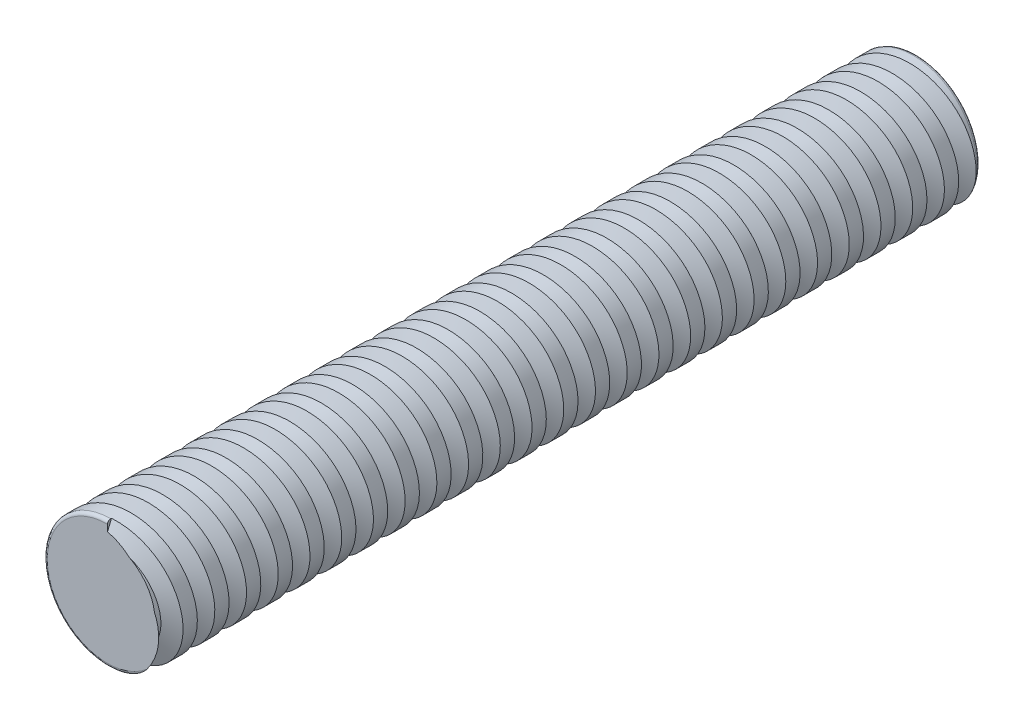
SolidWorks part; units mm, degrees
material "1.5714 (16NiCr4)"
ref_plane "Front Plane" through (0, 0, 0) normal (0, 0, 1) x (1, 0, 0)
ref_plane "Top Plane" through (0, 0, 0) normal (0, 1, 0) x (1, 0, 0)
ref_plane "Right Plane" through (0, 0, 0) normal (1, 0, 0) x (0, 0, -1)
sketch "Sketch1" plane through (0, 0, 0) normal (0, 0, 1) x (1, 0, 0)
  circle A0 centre (0, 0) radius 4
  dimension "D1" = 8
extrude "Boss-Extrude1" add sketch "Sketch1" against normal blind 51
fillet "Fillet1" radius 0.2 2 edges at (4, 0, -51) (4, 0, 0)
sketch "Sketch2" plane through (0, 0, 0) normal (0, 0, 1) x (1, 0, 0)
  circle A0 centre (0, 0) radius 4
  dimension "D1" = 8
sketch "Sketch3" plane through (0, 0, 0) normal (0, 1, 0) x (1, 0, 0)
  line L0 (3, 0.35) -> (3, 0.05)
  line L1 (3, 0.05) -> (5, -0.75)
  line L2 (5, -0.75) -> (5, 1.15)
  line L3 (5, 1.15) -> (3, 0.35)
  line L4 (5, 0.2) -> (3, 0.2)
  line L7 (4, 0.2) -> (-4, 0.2) construction
  point P7 (4, 0.2)
  dimension "D1" = 1.9
  dimension "D2" = 2
  dimension "D3" = 0.3
  dimension "D4" = 4
curve "Helix/Spiral1" pitch 2 height 200 turns 100
sweep "Cut-Sweep1" cut profiles "Sketch3" path "Helix/Spiral1"
